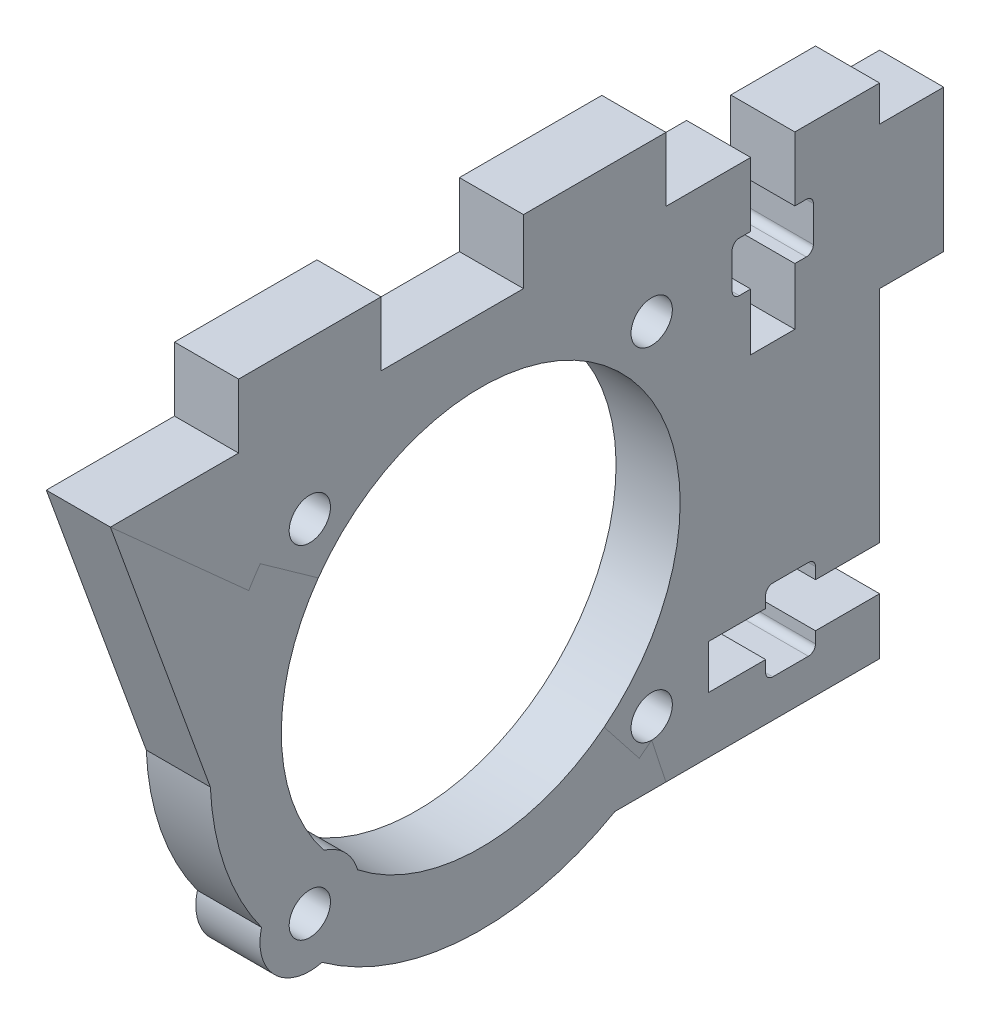
SolidWorks part; units mm, degrees
ref_plane "Front Plane" through (0, 0, 0) normal (0, 0, 1) x (1, 0, 0)
ref_plane "Top Plane" through (0, 0, 0) normal (0, 1, 0) x (1, 0, 0)
ref_plane "Right Plane" through (0, 0, 0) normal (1, 0, 0) x (0, 0, -1)
sketch "Sketch1" plane through (0, 0, 0) normal (1, 0, 0) x (0, 0, -1)
  line L0 (0, 0) -> (0, -35)
  line L1 (0, -35) -> (-54, 0)
  line L2 (-54, 0) -> (0, 0)
  dimension "D1" = 35
  dimension "D2" = 54
extrude "Boss-Extrude1" add sketch "Sketch1" along normal blind 4.5
sketch "Sketch2" plane through (4.5, 0, 0) normal (1, 0, 0) x (0, 0, -1)
  line L0 (0, -35) -> (0, 0) construction
  line L1 (-4.5, -2.5) -> (4.5, -2.5)
  line L2 (-4.5, -2.5) -> (-4.5, -12.5)
  line L3 (-4.5, -12.5) -> (4.5, -12.5)
  line L4 (4.5, -2.5) -> (4.5, -12.5)
  line L5 (-4.5, -2.5) -> (4.5, -12.5) construction
  line L6 (-4.5, -12.5) -> (4.5, -2.5) construction
  line L7 (0, 0) -> (-54, 0) construction
  point P0 (0, -7.5)
  dimension "D1" = 10
  dimension "D2" = 7.5
  dimension "D3" = 4.5
extrude "Boss-Extrude2" add sketch "Sketch2" against normal through all
sketch "Sketch3" plane through (4.5, 0, 0) normal (1, 0, 0) x (0, 0, -1)
  line L0 (0, -35) -> (-15, -35)
  line L1 (0, -25) -> (-54, 0)
  line L4 (0, -35) -> (0, -12.5) construction
  line L5 (0, -25) -> (0, -35)
  line L6 (-54, 0) -> (-15, -35)
  dimension "D1" = 15
  dimension "D2" = 10
extrude "Boss-Extrude3" add sketch "Sketch3" against normal through all
sketch "Sketch4" plane through (4.5, 0, 0) normal (1, 0, 0) x (0, 0, -1)
  line L0 (0, -29.5) -> (-12, -29.5) construction
  line L1 (0, -35) -> (0, -12.5) construction
  line L2 (0, -27.95) -> (-12, -27.95) construction
  line L3 (-12, -27.95) -> (-12, -31.05) construction
  line L4 (0, -31.05) -> (0, -27.95)
  line L5 (0, -27.95) -> (-4.5, -27.95)
  line L6 (-4.5, -27.95) -> (-4.5, -27.15)
  line L7 (-5, -26.65) -> (-7.5, -26.65)
  line L8 (-8, -27.15) -> (-8, -27.95)
  line L9 (-8, -27.95) -> (-12, -27.95)
  line L10 (-12, -27.95) -> (-12, -31.05)
  line L12 (0, -31.05) -> (-12, -31.05) construction
  line L13 (-8, -31.05) -> (-12, -31.05)
  line L14 (-8, -31.85) -> (-8, -31.05)
  line L15 (-5, -32.35) -> (-7.5, -32.35)
  line L16 (-4.5, -31.05) -> (-4.5, -31.85)
  line L17 (0, -31.05) -> (-4.5, -31.05)
  line L18 (4.5, -12.5) -> (4.5, -2.5) construction
  line L19 (0, -18.5) -> (-33.3857, -18.5) construction
  line L20 (-54, 0) -> (-15, -35) construction
  line L37 (0, -31.05) -> (-12, -31.05) construction
  arc A0 (-8, -31.85) -> (-7.5, -32.35) centre (-7.5, -31.85) ccw
  arc A1 (-5, -32.35) -> (-4.5, -31.85) centre (-5, -31.85) ccw
  arc A2 (-4.5, -27.15) -> (-5, -26.65) centre (-5, -27.15) ccw
  arc A3 (-7.5, -26.65) -> (-8, -27.15) centre (-7.5, -27.15) ccw
  point P10 (4.5, -7.5)
  point P20 (-8, -32.35)
  point P23 (-4.5, -32.35)
  point P26 (-4.5, -26.65)
  point P29 (-8, -26.65)
  dimension "D7" = 0.5
  dimension "D1" = 12
  dimension "D2" = 1.55
  dimension "D3" = 2.85
  dimension "D4" = 3.5
  dimension "D5" = 8
  dimension "D6" = 22
extrude "Cut-Extrude1" cut sketch "Sketch4" against normal through all
sketch "Sketch5" plane through (4.5, 0, 0) normal (1, 0, 0) x (0, 0, -1)
  line L0 (0, 0) -> (-54, 0) construction
  line L1 (-25, 4.5) -> (-15, 4.5)
  line L2 (-25, 4.5) -> (-25, 0)
  line L3 (0, 0) -> (-54, 0) construction
  line L4 (-15, 4.5) -> (-15, 0)
  line L5 (-25, 4.5) -> (-20, 0) construction
  line L6 (-20, 0) -> (-15, 4.5) construction
  line L7 (-30, 0) -> (-30, 4.5) construction
  line L8 (-40, 0) -> (-45, 4.5) construction
  line L9 (-35, 4.5) -> (-40, 0) construction
  line L10 (-45, 4.5) -> (-45, 0)
  line L12 (-35, 4.5) -> (-35, 0)
  line L13 (-35, 4.5) -> (-45, 4.5)
  line L14 (-20, 0) -> (-15, 4.5) construction
  line L15 (-15, 0) -> (-25, 0)
  line L16 (-35, 0) -> (-45, 0)
  point P0 (-20, 0)
  point P14 (-40, 0)
  dimension "D3" = 4.5
  dimension "D1" = 20
  dimension "D2" = 10
  dimension "D4" = 20
  dimension "D5" = 5
extrude "Boss-Extrude4" add sketch "Sketch5" against normal through all
sketch "Sketch8" [suppressed] plane through (4.5, 0, 0) normal (1, 0, 0) x (0, 0, -1)
  line L0 (-15, -30) -> (-27, -30) construction
  line L1 (-15, -35) -> (-27, -35)
  line L2 (-15, -25) -> (-27, -25)
  line L3 (-15, -35) -> (0, -35) construction
  line L4 (-15, -25) -> (-15, -35)
  arc A1 (-27, -25) -> (-27, -35) centre (-27, -30) ccw
  dimension "D5" = 5
  dimension "D1" = 0
  dimension "D2" = 12
  dimension "D3" = 0
  dimension "D4" = 10
extrude "Boss-Extrude5" [suppressed] add sketch "Sketch8" against normal up to surface (4.5 mm away) up to face at (0, -17.3125, 11.9375)
sketch "Sketch9" [suppressed] plane through (4.5, 0, 0) normal (1, 0, 0) x (0, 0, -1)
  line L0 (-27, -30) -> (-22, -30) construction
  line L1 (-27, -27) -> (-22, -27)
  line L2 (-27, -33) -> (-22, -33)
  arc A0 (-27, -27) -> (-27, -33) centre (-27, -30) ccw
  arc A1 (-22, -33) -> (-22, -27) centre (-22, -30) ccw
  point P3 (-24.5, -30)
  dimension "D1" = 3
  dimension "D2" = 5
extrude "Cut-Extrude3" [suppressed] cut sketch "Sketch9" against normal through all
sketch "Sketch10" plane through (0, 0, 0) normal (-1, 0, 0) x (0, 0, 1)
  line L0 (15, -35) -> (54, -12)
  line L1 (54, -12) -> (54, 0)
  line L3 (54, 0) -> (15, -35)
  dimension "D1" = 12
extrude "Boss-Extrude6" [suppressed] add sketch "Sketch10" against normal through all
sketch "Sketch6" plane through (4.5, 0, 0) normal (1, 0, 0) x (0, 0, -1)
  line L0 (-30, 0) -> (-30, -11) construction
  line L1 (-25, 0) -> (-35, 0) construction
  line L2 (-28.45, -11) -> (-31.55, -11) construction
  line L3 (-31.55, -11) -> (-31.55, 0) construction
  line L4 (-28.45, 0) -> (-31.55, 0)
  line L5 (-31.55, 0) -> (-31.55, -4.5)
  line L6 (-31.55, -4.5) -> (-32.35, -4.5)
  line L7 (-32.85, -5) -> (-32.85, -7.5)
  line L8 (-32.35, -8) -> (-31.55, -8)
  line L9 (-31.55, -8) -> (-31.55, -11)
  line L10 (-31.55, -11) -> (-28.45, -11)
  line L11 (-28.45, -11) -> (-28.45, 0) construction
  line L12 (-28.45, -8) -> (-28.45, -11)
  line L13 (-27.65, -8) -> (-28.45, -8)
  line L14 (-27.15, -5) -> (-27.15, -7.5)
  line L15 (-28.45, -4.5) -> (-27.65, -4.5)
  line L16 (-28.45, 0) -> (-28.45, -4.5)
  arc A0 (-32.85, -7.5) -> (-32.35, -8) centre (-32.35, -7.5) ccw
  arc A1 (-32.35, -4.5) -> (-32.85, -5) centre (-32.35, -5) ccw
  arc A2 (-27.65, -4.5) -> (-27.15, -5) centre (-27.65, -5) cw
  arc A3 (-27.15, -7.5) -> (-27.65, -8) centre (-27.65, -7.5) cw
  point P12 (-32.85, -8)
  point P15 (-32.85, -4.5)
  point P26 (-27.15, -4.5)
  point P27 (-27.15, -8)
  dimension "D2" = 1.55
  dimension "D4" = 3.5
  dimension "D6" = 0.5
  dimension "D1" = 11
  dimension "D3" = 8
  dimension "D5" = 2.85
extrude "Cut-Extrude2" [suppressed] cut sketch "Sketch6" against normal through all
sketch "Sketch11" plane through (0, 0, 0) normal (-1, 0, 0) x (0, 0, 1)
  line L0 (7.5, 0) -> (7.5, -12) construction
  line L1 (0, 0) -> (15, 0) construction
  line L2 (5.95, -12) -> (9.05, -12)
  line L3 (9.05, -12) -> (9.05, -8)
  line L4 (9.05, -8) -> (9.85, -8)
  line L5 (10.35, -7.5) -> (10.35, -5)
  line L6 (9.85, -4.5) -> (9.05, -4.5)
  line L7 (9.05, -4.5) -> (9.05, 0)
  line L8 (9.05, 0) -> (5.95, 0)
  line L9 (9.05, -8) -> (9.05, -4.5) construction
  line L10 (0, 0) -> (15, 0) construction
  line L11 (5.95, -8) -> (5.95, -4.5) construction
  line L12 (5.95, -4.5) -> (5.95, 0)
  line L13 (5.15, -4.5) -> (5.95, -4.5)
  line L14 (4.65, -7.5) -> (4.65, -5)
  line L15 (5.95, -8) -> (5.15, -8)
  line L16 (5.95, -12) -> (5.95, -8)
  arc A0 (10.35, -5) -> (9.85, -4.5) centre (9.85, -5) ccw
  arc A1 (5.15, -4.5) -> (4.65, -5) centre (5.15, -5) ccw
  arc A2 (9.85, -8) -> (10.35, -7.5) centre (9.85, -7.5) ccw
  arc A3 (4.65, -7.5) -> (5.15, -8) centre (5.15, -7.5) ccw
  point P11 (7.5, 0)
  point P22 (10.35, -4.5)
  point P25 (4.65, -4.5)
  point P28 (10.35, -8)
  point P31 (4.65, -8)
  dimension "D7" = 0.5
  dimension "D1" = 12
  dimension "D3" = 2.85
  dimension "D8" = 0.5
  dimension "D2" = 3.5
  dimension "D4" = 8
  dimension "D5" = 1.55
  dimension "D6" = 0
extrude "Cut-Extrude4" cut sketch "Sketch11" against normal through all
sketch "Sketch12" plane through (0, 0, 0) normal (-1, 0, 0) x (0, 0, 1)
  line L0 (28, -18.5) -> (16, -6.5) construction
  line L1 (28, -18.5) -> (28, -4.5) construction
  line L2 (28, -18.5) -> (40, -6.5) construction
  line L3 (28, -18.5) -> (14, -18.5) construction
  line L4 (28, -18.5) -> (16, -30.5) construction
  line L5 (28, -18.5) -> (16, -6.5) construction
  line L6 (0, -27.95) -> (0, -12.5) construction
  line L7 (25, 0) -> (35, 0) construction
  circle A0 centre (28, -18.5) radius 14
  circle A1 centre (16, -6.5) radius 1.45
  circle A2 centre (40, -6.5) radius 1.45
  circle A3 centre (16, -30.5) radius 1.45
  dimension "D1" = 28
  dimension "D2" = 2.9
  dimension "D3" = 12
  dimension "D4" = 45
  dimension "D5" = 28
  dimension "D6" = 18.5
extrude "FanCutout" cut sketch "Sketch12" against normal through all
sketch "Sketch13" plane through (0, 0, 0) normal (-1, 0, 0) x (0, 0, 1)
  line L0 (39.4071, -10.3834) -> (43.481, -7.4847)
  line L1 (19.3358, -29.4969) -> (16.2414, -33.4243)
  line L6 (28, -18.5) -> (54, 0) construction
  line L7 (28, -18.5) -> (15, -35) construction
  arc A0 (19.3358, -29.4969) -> (39.4071, -10.3834) centre (28, -18.5) ccw
  arc A1 (16.2414, -33.4243) -> (43.481, -7.4847) centre (28, -18.5) ccw
  arc A3 (40.4722, -12.1404) -> (20.333, -30.214) centre (28, -18.5) ccw construction
  dimension "D1" = 5
extrude "Boss-Extrude7" add sketch "Sketch13" against normal through all
sketch "Sketch14" plane through (0, 0, 0) normal (-1, 0, 0) x (0, 0, 1)
  line L0 (28, -4.5) -> (28, -32.5) construction
  line L1 (28, -18.5) -> (40, -30.5) construction
  circle A0 centre (28, -18.5) radius 14 construction
  circle A1 centre (40, -30.5) radius 3.5
  dimension "D2" = 7
  dimension "D1" = 45
  dimension "D3" = 12
extrude "Boss-Extrude8" add sketch "Sketch14" against normal through all
sketch "Sketch15" plane through (0, 0, 0) normal (-1, 0, 0) x (0, 0, 1)
  line L0 (42.4749, -32.9749) -> (28, -18.5) construction
  arc A0 (39.1388, -33.8924) -> (43.3924, -29.6388) centre (40, -30.5) ccw construction
  circle A1 centre (40, -30.5) radius 1.45
  dimension "D1" = 2.9
extrude "Cut-Extrude6" cut sketch "Sketch15" against normal through all
sketch "Sketch16" [suppressed] plane through (4.5, 0, 0) normal (1, 0, 0) x (0, 0, -1)
  line L0 (0, -34.5) -> (-39, -34.5) construction
  line L1 (0, -27.95) -> (0, -12.5) construction
  line L2 (-15, -34.5) -> (-39, -34.5) construction
  line L3 (-15, -38.5) -> (-39, -38.5)
  line L4 (-15, -30.5) -> (-39, -30.5)
  arc A0 (-15, -38.5) -> (-15, -30.5) centre (-15, -34.5) ccw
  arc A1 (-39, -30.5) -> (-39, -38.5) centre (-39, -34.5) ccw
  point P5 (-27, -34.5)
  point P12 (0, -20.225)
  dimension "D1" = 4
  dimension "D2" = 34.5
  dimension "D3" = 39
  dimension "D4" = 15
extrude "Boss-Extrude9" [suppressed] add sketch "Sketch16" against normal through all
sketch "Sketch17" [suppressed] plane through (4.5, 0, 0) normal (1, 0, 0) x (0, 0, -1)
  line L0 (-43, -34.5) -> (0, -34.5) construction
  line L1 (0, -27.75) -> (0, -12.5) construction
  line L2 (-26.5, -34.5) -> (-26.5, -20.0064) construction
  arc A0 (-42.1823, -32.0766) -> (-39, -38.5) centre (-39, -34.5) ccw construction
  circle A1 centre (-39, -34.5) radius 1.55
  circle A2 centre (-14, -34.5) radius 1.55
  dimension "D1" = 2.9
  dimension "D2" = 12.5
extrude "Cut-Extrude7" [suppressed] cut sketch "Sketch17" against normal through all
sketch "Sketch18" [suppressed] plane through (4.5, 0, 0) normal (1, 0, 0) x (0, 0, -1)
  line L0 (-15, -38.5) -> (0, -35)
  line L1 (0, -35) -> (-11.0314, -35)
  line L2 (-11.0314, -35) -> (-15, -38.5)
extrude "Boss-Extrude10" [suppressed] add sketch "Sketch18" against normal through all
sketch "Sketch20" [suppressed] plane through (4.5, 0, 0) normal (1, 0, 0) x (0, 0, -1)
  line L0 (0, -35) -> (0, -31.05) construction
  line L1 (-9, -38) -> (-37.9081, -38)
  line L2 (-40.7232, -36.0371) -> (-54, 0)
  line L3 (-54, 0) -> (-15, -35)
  line L4 (-15, -35) -> (-6, -35)
  line L5 (-9, -38) -> (-6, -35)
  line L6 (-40.7232, -36.0371) -> (-40, -38) construction
  line L7 (-40, -38) -> (-37.9081, -38) construction
  arc A1 (-37.9081, -38) -> (-40.7232, -36.0371) centre (-37.9081, -35) cw
  point P0 (0, -33.025)
  point P14 (-40, -38)
  dimension "D3" = 6
  dimension "D4" = 3
  dimension "D1" = 40
  dimension "D2" = 3
  dimension "D5" = 135
extrude "Boss-Extrude11" [suppressed] add sketch "Sketch20" against normal through all
sketch "Sketch21" [suppressed] plane through (4.5, 0, 0) normal (1, 0, 0) x (0, 0, -1)
  line L0 (0, -34.5) -> (-41.2895, -34.5) construction
  line L1 (0, -35) -> (0, -31.05) construction
  line L2 (-54, 0) -> (-40.7232, -36.0371) construction
  line L3 (0, -27.95) -> (0, -12.5) construction
  circle A0 centre (-36, -34.5) radius 1.45
  circle A1 centre (-11, -34.5) radius 1.45
  dimension "D2" = 2.9
  dimension "D3" = 2.9
  dimension "D1" = 25
  dimension "D4" = 34.5
  dimension "D5" = 11
extrude "Cut-Extrude8" [suppressed] cut sketch "Sketch21" against normal through all
sketch "Sketch22" [suppressed] plane through (4.5, 0, 0) normal (1, 0, 0) x (0, 0, -1)
  line L0 (0, -27.95) -> (0, -12.5) construction
  line L1 (-25, 0) -> (-35, 0) construction
  circle A0 centre (-28, -18) radius 13.25
  dimension "D2" = 18
  dimension "D3" = 26.5
  dimension "D1" = 28
extrude "Cut-Extrude9" [suppressed] cut sketch "Sketch22" against normal through all
sketch "Sketch24" plane through (0, 0, 0) normal (-1, 0, 0) x (0, 0, 1)
  line L0 (15, -35) -> (20, -35)
  line L1 (20, -35) -> (16, -31.95)
  line L2 (16, -31.95) -> (15, -35)
  circle A0 centre (16, -30.5) radius 1.45 construction
  dimension "D1" = 5
extrude "Boss-Extrude13" add sketch "Sketch24" against normal through all
sketch "Sketch25" plane through (0, 0, 0) normal (-1, 0, 0) x (0, 0, 1)
  line L0 (54, 0) -> (46.9826, -19.3121)
  line L1 (46.9826, -19.3121) -> (44.2874, -8.7164)
  line L2 (44.2874, -8.7164) -> (54, 0)
  arc A0 (43.3924, -29.6388) -> (44.2874, -8.7164) centre (28, -18.5) ccw construction
extrude "Boss-Extrude15" add sketch "Sketch25" against normal through all
equation "\"X-ROD-SPACING\"=45"
equation "\"Y-ROD-SPACING\"=75"
equation "\"Z-ROD-SPACING\"=17.5"
equation "\"Y-BED-OFFSET\"=2"
equation "\"Y-BED-ROD-INSET\"=3.5"
equation "\"Y-BED-SCREW-SPACING\"=209"
equation "\"Y-BED-SCREW-CUTOUT-SLOT-HEIGHT\"=2"
equation "\"T-SLOT-NUT-FILLET-RADIUS\"=0.5"
equation "\"T-SLOT-SCREW-SHAFT-RADIUS\"=1.55"
equation "\"T-SLOT-SCREW-SHAFT-CUTOUT-LENGTH\"=11"
equation "\"T-SLOT-NUT-DEPTH\"=3.5"
equation "\"T-SLOT-NUT-WIDTH\"=2.85"
equation "\"T-SLOT-NUT-END-DISTANCE\"=8"
equation "\"ACRYLIC-THICKNESS\"=10"
equation "\"ACRYLIC-THICKNESS2\"=4.5"
equation "\"ACRYLIC-TAB-CUTOUT-SIZE\"=\"ACRYLIC-THICKNESS\"+\"ACRYLIC-TAB-TOLERANCE\"*2"
equation "\"ACRYLIC-TAB-WIDTH\"=\"ACRYLIC-THICKNESS\""
equation "\"ACRYLIC-M3-HOLE\"=2.9"
equation "\"SMOOTHROD-CAP-SCREW-DISTANCE\"=20"
equation "\"FRAME-WIDTH-INNER\"=370"
equation "\"NEMA17-HOLE-SPACING\"=31"
equation "\"NEMA17-CENTRAL-CUTOUT\"=22.5"
equation "\"Z-BRACKET-REACH\"=57"
equation "\"Z-ROD-INSET\"=13.5"
equation "\"TOP-BRACKET-SPACING\"=40"
equation "\"SMOOTHROD-X-LENGTH\"=350"
equation "\"SMOOTHROD-Y-LENGTH\"=350"
equation "\"SMOOTHROD-Z-LENGTH\"=350"
equation "\"SMOOTHROD-TIGHTENING-HEADROOM\"=.25"
equation "\"LEADSCREW-Z-LENGTH\"=300"
equation "\"SCREW-LENGTH-FRAME\"=\"ACRYLIC-THICKNESS\" + 10"
equation "\"SCREW-LENGTH-MOTOR\"=\"ACRYLIC-THICKNESS\" + 5"
equation "\"SCREW-LENGTH-EXTRUDER\"=28"
equation "\"SCREW-HEAD-RADIUS\"=6"
equation "\"PRINTED-X-SMOOTHROD-DIAMETER\"=8.8"
equation "\"PRINTED-X-SMOOTHROD-CUTOUT\"=10"
equation "\"PRINTED-X-BASE-HEIGHT\"=10"
equation "\"PRINTED-LM8UU-CUTOUT-SIZE\"=15.5"
equation "\"PRINTED-LM8UU-CUTOUT-LENGTH\"=24.5"
equation "\"PRINTED-X-IDLER-HEIGHT\"=16"
equation "\"PSU-MOUNTING-WIDTH\"=95"
equation "\"PSU-MOUNTING-HEIGHT\"=177"
equation "\"Y-BELT-TO-ROD-DISTANCE\"=20"
equation "\"SPOOL-HOLDER-ROD-SPACING\"=150"
equation "\"ACRYLIC-X-CARRIAGE-WIDTH\"=55"
equation "\"ACRYLIC-X-CARRIAGE-HEIGHT\"=75"
equation "\"ACRYLIC-X-CARRIAGE-SCREW-SPACING-X\"=15"
equation "\"ACRYLIC-X-CARRIAGE-SCREW-SPACING-Y\"=33"
equation "\"ACRYLIC-X-CARRIAGE-CENTER-TAB-SPACING\"=14"
equation "\"ACRYLIC-X-CARRIAGE-EXTRUDER-SHELF-DEPTH\"=\"ACRYLIC-X-CARRIAGE-EXTRUDER-OFFSET\" + 28"
equation "\"D2@Sketch1\"=\"ACRYLIC-X-CARRIAGE-EXTRUDER-SHELF-DEPTH\""
equation "\"D1@Boss-Extrude1\"=\"ACRYLIC-THICKNESS2\""
equation "\"D1@Sketch2\"=\"ACRYLIC-TAB-WIDTH\""
equation "\"D3@Sketch2\"=\"ACRYLIC-THICKNESS2\""
equation "\"ACRYLIC-X-CARRIAGE-LM8UU-CUTOUT-WIDTH\"=24.25"
equation "\"ACRYLIC-X-CARRIAGE-EXTRUDER-BRACE-SPACING\"=23"
equation "\"ACRYLIC-X-CARRIAGE-EXTRUDER-BRACE-HEIGHT\"=35"
equation "\"D1@Sketch1\"=\"ACRYLIC-X-CARRIAGE-EXTRUDER-BRACE-HEIGHT\""
equation "\"D1@Sketch4\"=\"T-SLOT-SCREW-SHAFT-CUTOUT-LENGTH\"+1"
equation "\"D2@Sketch4\"=\"T-SLOT-SCREW-SHAFT-RADIUS\""
equation "\"D3@Sketch4\"=\"T-SLOT-NUT-WIDTH\""
equation "\"D4@Sketch4\"=\"T-SLOT-NUT-DEPTH\""
equation "\"D5@Sketch4\"=\"T-SLOT-NUT-END-DISTANCE\""
equation "\"D7@Sketch4\"=\"T-SLOT-NUT-FILLET-RADIUS\""
equation "\"ACRYLIC-X-CARRIAGE-EXTRUDER-BRACE-SCREW-SPACING\"=22"
equation "\"D6@Sketch4\"=\"ACRYLIC-X-CARRIAGE-EXTRUDER-BRACE-SCREW-SPACING\""
equation "\"ACRYLIC-X-CARRIAGE-EXTRUDER-BRACE-TAB-OFFSET\"=20"
equation "\"D1@Sketch5\"=\"ACRYLIC-X-CARRIAGE-EXTRUDER-BRACE-TAB-OFFSET\""
equation "\"D2@Sketch5\"=\"ACRYLIC-TAB-WIDTH\""
equation "\"D3@Sketch5\"=\"ACRYLIC-THICKNESS2\""
equation "\"ACRYLIC-X-CARRIAGE-EXTRUDER-OFFSET\"=26"
equation "\"ACRYLIC-X-CARRIAGE-EXTRUDER-ANGLE\"=90"
equation "\"D1@Sketch6\"=\"T-SLOT-SCREW-SHAFT-CUTOUT-LENGTH\""
equation "\"D2@Sketch6\"=\"T-SLOT-SCREW-SHAFT-RADIUS\""
equation "\"D3@Sketch6\"=\"T-SLOT-NUT-END-DISTANCE\""
equation "\"D4@Sketch6\"=\"T-SLOT-NUT-DEPTH\""
equation "\"D5@Sketch6\"=\"T-SLOT-NUT-WIDTH\""
equation "\"D6@Sketch6\"=\"T-SLOT-NUT-FILLET-RADIUS\""
equation "\"D1@Sketch11\"=\"T-SLOT-SCREW-SHAFT-CUTOUT-LENGTH\"+1"
equation "\"D2@Sketch11\"=\"T-SLOT-NUT-DEPTH\""
equation "\"D3@Sketch11\"=\"T-SLOT-NUT-WIDTH\""
equation "\"D4@Sketch11\"=\"T-SLOT-NUT-END-DISTANCE\""
equation "\"D5@Sketch11\"=\"T-SLOT-SCREW-SHAFT-RADIUS\""
equation "\"D7@Sketch11\"=\"T-SLOT-NUT-FILLET-RADIUS\""
equation "\"D8@Sketch11\"=\"T-SLOT-NUT-FILLET-RADIUS\""
equation "\"D2@Sketch12\"=\"ACRYLIC-M3-HOLE\""
equation "\"D1@Sketch15\"=\"ACRYLIC-M3-HOLE\""
equation "\"D1@Sketch17\"=\"ACRYLIC-M3-HOLE\""
equation "\"D2@Sketch21\"=\"ACRYLIC-M3-HOLE\""
equation "\"D3@Sketch21\"=\"ACRYLIC-M3-HOLE\""
